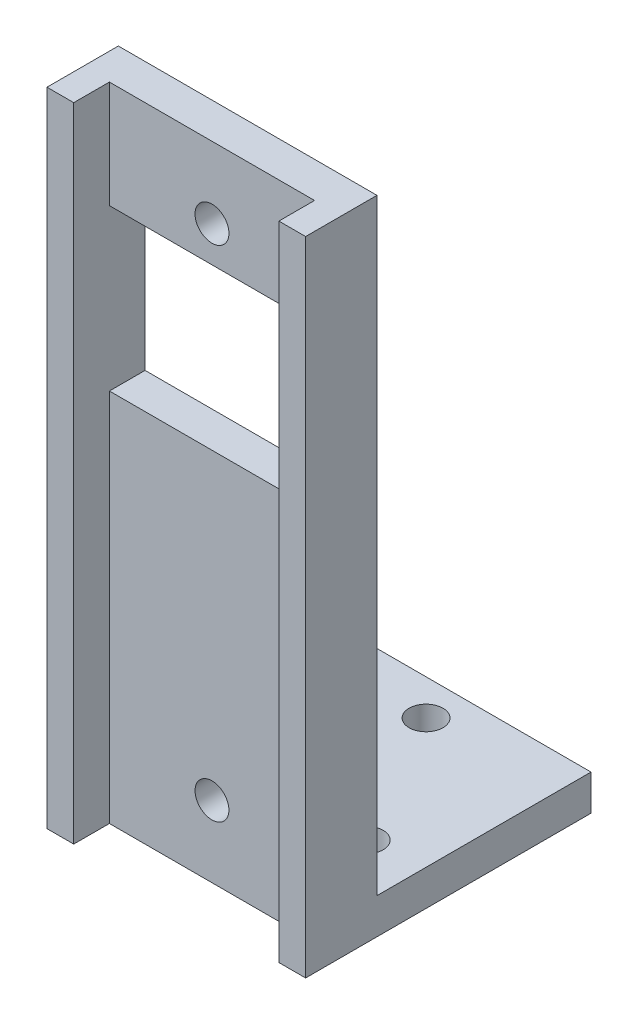
SolidWorks part; units mm, degrees
ref_plane "Front Plane" through (0, 0, 0) normal (0, 0, 1) x (1, 0, 0)
ref_plane "Top Plane" through (0, 0, 0) normal (0, 1, 0) x (1, 0, 0)
ref_plane "Right Plane" through (0, 0, 0) normal (1, 0, 0) x (0, 0, -1)
ref_axis "X-Axis" through (-88.99, 0, 0) along (1, 0, 0)
ref_axis "Y-Axis" through (0, 55, 0) along (0, -1, 0)
ref_axis "Z-Axis" through (0, 0, -88.99) along (0, 0, 1)
sketch "Sketch1" plane through (0, 0, 0) normal (0, 0, 1) x (1, 0, 0)
  line L1 (-7.25, 18) -> (7.25, 18)
  line L2 (-7.25, 18) -> (-7.25, -18)
  line L3 (-7.25, -18) -> (7.25, -18)
  line L4 (7.25, 18) -> (7.25, -18)
  line L5 (-7.25, 18) -> (7.25, -18) construction
  line L6 (-7.25, -18) -> (7.25, 18) construction
  point P0 (0, 0)
  dimension "D1" = 14.5
  dimension "D2" = 36
extrude "Boss-Extrude1" add sketch "Sketch1" along normal blind 4
sketch "Sketch3" plane through (0, -18, 0) normal (0, -1, 0) x (1, 0, 0)
  line L0 (7.25, 4) -> (7.25, -12) construction
  line L2 (-7.25, 4) -> (7.25, 4)
  line L3 (-7.25, 4) -> (-7.25, -12)
  line L4 (-7.25, -12) -> (7.25, -12)
  line L5 (7.25, 4) -> (7.25, -12)
  dimension "D1" = 16
extrude "Boss-Extrude2" add sketch "Sketch3" against normal blind 2
sketch "Sketch2" plane through (0, 0, 4) normal (0, 0, 1) x (1, 0, 0)
  line L0 (7.25, 18) -> (-7.25, 18) construction
  line L1 (-5.75, 18) -> (5.75, 18)
  line L2 (-5.75, 18) -> (-5.75, -18)
  line L3 (-5.75, -18) -> (5.75, -18)
  line L4 (5.75, 18) -> (5.75, -18)
  line L5 (-7.25, -18) -> (7.25, -18) construction
  line L6 (-7.25, 18) -> (-5.75, 18) construction
  line L7 (5.75, 18) -> (7.25, 18) construction
  dimension "D1" = 11.5
extrude "Cut-Extrude1" cut sketch "Sketch2" against normal offset from surface (2 mm away) 2 up to face at (0, 1, 0)
sketch "Sketch4" plane through (0, 0, 2) normal (0, 0, 1) x (1, 0, 0)
  line L0 (0, 18) -> (0, 13.05) construction
  line L1 (-5.75, 18) -> (5.75, 18) construction
  line L2 (5.75, -18) -> (-5.75, -18) construction
  line L3 (0, -13.05) -> (0, -18) construction
  line L4 (0, -13.05) -> (0, 13.05) construction
  circle A0 centre (0, -14) radius 0.95
  circle A1 centre (0, 14) radius 0.95
  dimension "D2" = 1.9
  dimension "D1" = 28
extrude "Cut-Extrude2" cut sketch "Sketch4" against normal through all
sketch "Sketch5" plane through (0, 0, 2) normal (0, 0, 1) x (1, 0, 0)
  line L0 (-5.75, -18) -> (-5.75, 18) construction
  line L1 (-5.75, 12) -> (5.75, 12)
  line L2 (-5.75, 12) -> (-5.75, 3)
  line L3 (-5.75, 3) -> (5.75, 3)
  line L4 (5.75, 12) -> (5.75, 3)
  line L5 (5.75, 18) -> (5.75, -18) construction
  line L6 (-5.75, 18) -> (5.75, 18) construction
  dimension "D1" = 6
  dimension "D2" = 9
extrude "Cut-Extrude3" cut sketch "Sketch5" against normal through all
sketch "Sketch6" plane through (0, -16, 0) normal (0, 1, 0) x (1, 0, 0)
  line L0 (-7.25, 2.3952) -> (-4.25, 2.3952) construction
  line L1 (-7.25, 0) -> (-7.25, 12) construction
  line L2 (-4.25, 2.3952) -> (4.25, 2.3952) construction
  line L3 (4.25, 2.3952) -> (7.25, 2.3952) construction
  line L4 (7.25, 12) -> (7.25, 0) construction
  line L5 (0, 12) -> (0, 10) construction
  line L6 (-7.25, 12) -> (7.25, 12) construction
  circle A0 centre (-4.25, 2.3952) radius 0.95
  circle A1 centre (4.25, 2.3952) radius 0.95
  circle A2 centre (0, 10) radius 0.95
  dimension "D1" = 1.9
  dimension "D2" = 3
  dimension "D3" = 2
extrude "Cut-Extrude4" cut sketch "Sketch6" against normal through all
equation "\"D1@Sketch1\"=11+3+0.5"
equation "\"D2@Sketch1\"=28+8"
